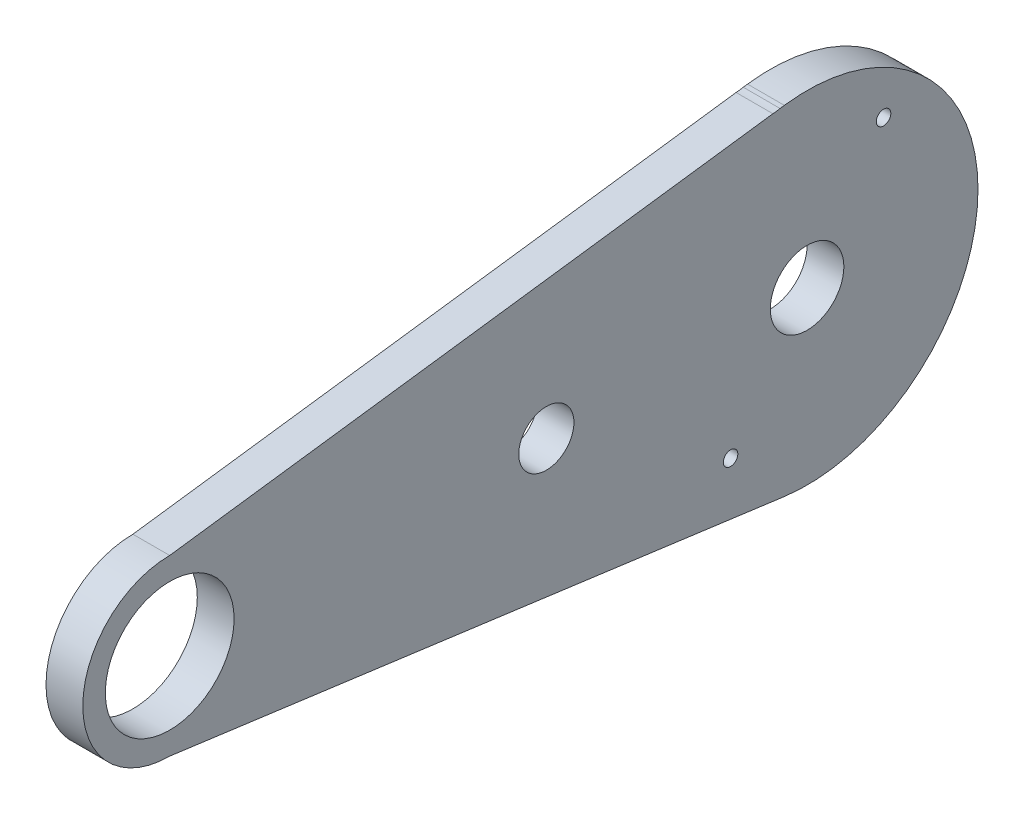
SolidWorks part; units mm, degrees
ref_plane "Front Plane" through (0, 0, 0) normal (0, 0, 1) x (1, 0, 0)
ref_plane "Top Plane" through (0, 0, 0) normal (0, 1, 0) x (1, 0, 0)
ref_plane "Right Plane" through (0, 0, 0) normal (1, 0, 0) x (0, 0, -1)
sketch "Sketch1" plane through (0, 0, 0) normal (1, 0, 0) x (0, 0, -1)
  line L4 (0, 15) -> (0, 11.1125) construction
  line L6 (0, 11.1125) -> (0, -11.1125) construction
  line L7 (0, -11.1125) -> (0, -15) construction
  line L8 (0, 15) -> (106.0756, 29.2378)
  line L9 (0, -15) -> (106.0756, -29.2378)
  line L10 (-4.0667, 14.4382) -> (101.5842, 44.1959)
  line L11 (130.6993, 21.0188) -> (109.1354, 42.2549)
  circle A0 centre (110, 0) radius 6.35
  circle A1 centre (0, 0) radius 11.1125
  arc A3 (106.0756, -29.2378) -> (106.0756, 29.2378) centre (110, 0) ccw
  arc A5 (0, 15) -> (0, -15) centre (0, 0) ccw
  arc A6 (106.0756, 29.2378) -> (106.0756, -29.2378) centre (110, 0) ccw construction
  arc A7 (0, -15) -> (0, 15) centre (0, 0) ccw construction
  circle A8 centre (0, 0) radius 110 construction
  circle A9 centre (0, 0) radius 100 construction
  circle A10 centre (103.6887, 36.7241) radius 4.7625
  circle A11 centre (103.6887, 36.7241) radius 7.7625
  dimension "D3" = 22.225
  dimension "D4" = 9.525
  dimension "D5" = 12.7
  dimension "D6" = 59
  dimension "D7" = 3
  dimension "D1" = 10
  dimension "D2" = 110
  dimension "D9" = 30
extrude "Boss-Extrude1" add sketch "Sketch1" along normal mid plane 6.35 contours A11 L8 A5 L9 A3 A0 A1 region at (0, -0.0001, -73.7166)
hole_wizard "M3x0.5 Tapped Hole1" positions "Sketch2" profile "Sketch3" tap size "M3x0.5" standard "ANSI Metric" end condition through all
sketch "Sketch2" plane through (3.175, 0, 0) normal (1, 0, 0) x (0, 0, -1)
  line L0 (96.7991, -18.8528) -> (123.2009, 18.8528) construction
  line L2 (3.4925, 0) -> (-3.4925, 0) construction
  line L3 (0, 0) -> (110, 0) construction
  circle A1 centre (110, 0) radius 6.35 construction
  point P0 (123.2009, 18.8528)
  point P12 (110, 0)
  point P13 (96.7991, -18.8528)
  point P32 (0, 0)
  point P33 (0, 0)
  point P34 (0, 0)
  dimension "D1" = 23.015
  dimension "D2" = 125
sketch "Sketch3" plane through (3.175, 18.8528, -123.2009) normal (0, 1, 0) x (0, 0, -1)
  line L0 (0, 0) -> (0, 6.35)
  line L1 (0, 6.35) -> (1.25, 6.35)
  line L2 (1.25, 6.35) -> (1.25, 0)
  line L5 (1.25, 0) -> (0, 0)
  line L11 (0, -6.35) -> (0, 107.95) construction
  dimension "Thru Tap Drill Dia." = 2.5
  dimension "Thru Tap Drill Depth" = 6.35
cosmetic thread "Hole Thread1" parameters "D2"=3
cosmetic thread "Hole Thread2" parameters "D2"=3
hole_wizard "3/8 (0.3750) Dowel Hole1" positions "Sketch4" profile "Sketch5" hole size "3/8" standard "ANSI Inch" end condition through all
sketch "Sketch4" plane through (3.175, 0, 0) normal (1, 0, 0) x (0, 0, -1)
  point P0 (65, 0)
  dimension "D1" = 65
sketch "Sketch5" plane through (3.175, 0, -65) normal (0, 1, 0) x (0, 0, -1)
  line L0 (0, 0) -> (0, 6.35)
  line L1 (0, 6.35) -> (4.7625, 6.35)
  line L2 (4.7625, 6.35) -> (4.7625, 0)
  line L5 (4.7625, 0) -> (0, 0)
  line L11 (0, -6.35) -> (0, 107.95) construction
  dimension "Thru Hole Dia." = 9.525
  dimension "Thru Hole Depth" = 6.35
